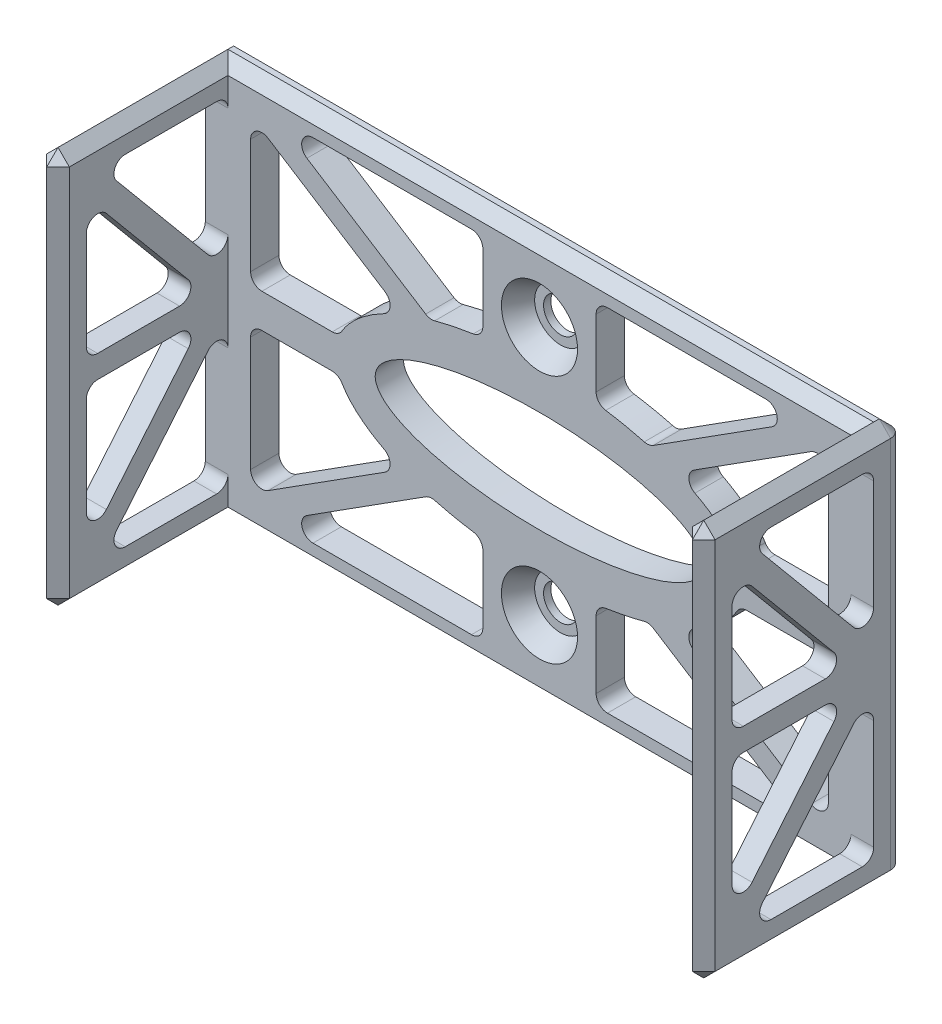
SolidWorks part; units mm, degrees
material "6061-T6 (SS)"
ref_plane "Front Plane" through (0, 0, 0) normal (0, 0, 1) x (1, 0, 0)
ref_plane "Top Plane" through (0, 0, 0) normal (0, 1, 0) x (1, 0, 0)
ref_plane "Right Plane" through (0, 0, 0) normal (1, 0, 0) x (0, 0, -1)
sketch "Sketch1" plane through (0, 0, 0) normal (0, 0, 1) x (1, 0, 0)
  line L1 (-55, 35) -> (55, 35)
  line L2 (-55, 35) -> (-55, -35)
  line L3 (-55, -35) -> (55, -35)
  line L4 (55, 35) -> (55, -35)
  line L5 (-55, 35) -> (55, -35) construction
  line L6 (-55, -35) -> (55, 35) construction
  circle A0 centre (0, 22) radius 3
  circle A1 centre (0, -22) radius 3
  point P0 (0, 0)
  dimension "D4" = 6
  dimension "D5" = 6
  dimension "D1" = 70
  dimension "D2" = 110
  dimension "D3" = 13
  dimension "D6" = 13
extrude "Boss-Extrude1" add sketch "Sketch1" along normal blind 5
sketch "Sketch2" plane through (0, 0, 5) normal (0, 0, 1) x (1, 0, 0)
  circle A0 centre (0, 22) radius 6.72
  circle A1 centre (0, -22) radius 6.72
  dimension "D1" = 13.44
  dimension "D2" = 13.44
extrude "Cut-Extrude1" cut sketch "Sketch2" against normal blind 3.72 draft 30
sketch "Sketch3" plane through (0, 0, 5) normal (0, 0, 1) x (1, 0, 0)
  line L0 (0, 0) -> (-55, 35) construction
  line L1 (0, 0) -> (-55, -35) construction
  line L2 (0, 0) -> (-13.5, 0) construction
  line L4 (-13.5, 0) -> (55, 0) construction
  line L5 (55, -35) -> (55, 35) construction
  line L6 (0, 0) -> (55, -35) construction
  line L7 (0, 0) -> (55, 35) construction
  line L8 (0, 0) -> (-55, 0) construction
  line L9 (-55, 35) -> (-55, -35) construction
  line L10 (-51, 28.8986) -> (-51, 3)
  line L11 (-51, 3) -> (-10.3022, 3)
  line L12 (-10.3022, 3) -> (-51, 28.8986)
  line L13 (-51, -3) -> (-51, -28.8986)
  line L14 (-51, -28.8986) -> (-10.3022, -3)
  line L15 (-10.3022, -3) -> (-51, -3)
  line L16 (-46.8517, 31) -> (-10, 7.5489)
  line L17 (-10, 7.5489) -> (-10, 31)
  line L18 (-10, 31) -> (-46.8517, 31)
  line L19 (-10, -7.5489) -> (-46.8517, -31)
  line L20 (-46.8517, -31) -> (-10, -31)
  line L21 (-10, -31) -> (-10, -7.5489)
  line L22 (0, 35) -> (0, -35) construction
  line L25 (-0.8631, 0.5493) -> (-0.8369, -0.5325) construction
  line L26 (55, 35) -> (-55, 35) construction
  line L27 (-55, -35) -> (55, -35) construction
  line L28 (46.8517, -31) -> (10, -31)
  line L29 (10, -7.5489) -> (46.8517, -31)
  line L30 (10, -31) -> (10, -7.5489)
  line L31 (51, -28.8986) -> (10.3022, -3)
  line L32 (51, -3) -> (51, -28.8986)
  line L33 (10.3022, -3) -> (51, -3)
  line L34 (51, 3) -> (10.3022, 3)
  line L35 (51, 28.8986) -> (51, 3)
  line L36 (10.3022, 3) -> (51, 28.8986)
  line L37 (10, 7.5489) -> (10, 31)
  line L38 (46.8517, 31) -> (10, 7.5489)
  line L39 (10, 31) -> (46.8517, 31)
  ellipse E0 centre (0, 0) end of major axis (36, 0) minor radius 16
  point P38 (-10, 19.2745)
  point P39 (-27.5, 0)
  point P40 (-30.6511, -15.9493)
  dimension "D2" = 4
  dimension "D3" = 10
  dimension "D4" = 4
  dimension "D5" = 1
  dimension "D6" = 3
  dimension "D7" = 3
  dimension "D8" = 3
  dimension "D9" = 3
  dimension "D10" = 1
  dimension "D11" = 4
  dimension "D12" = 10
  dimension "D13" = 19
  dimension "D14" = 19
extrude "Cut-Extrude2" cut sketch "Sketch3" against normal through all contours E0 L17 L18 L16 | E0 L12 L10 L11 | E0 L15 L13 L14 | E0 L19 L20 L21 | E0 L30 L28 L29 | E0 L31 L32 L33 | E0 L34 L35 L36 | E0 L38 L39 L37 region at (-41.5374, 13.3204, 5) region at (-23.1546, 24.2306, 5) region at (-41.5374, -13.3204, 5) region at (23.1546, 24.2306, 5) region at (-23.1546, -24.2306, 5) region at (41.5374, 13.3204, 5) region at (23.1546, -24.2306, 5) region at (41.5374, -13.3204, 5)
sketch "Sketch5" plane through (0, 0, 5) normal (0, 0, 1) x (1, 0, 0)
  ellipse E0 centre (0, 0) end of major axis (29, 0) minor radius 9
  dimension "D1" = 7
  dimension "D2" = 7
extrude "Cut-Extrude3" cut sketch "Sketch5" against normal through all
sketch "Sketch6" plane through (-55, 0, 0) normal (-1, 0, 0) x (0, 0, 1)
  line L0 (5, -35) -> (0, -35) construction
  line L1 (0, 35) -> (35, 35)
  line L2 (0, 35) -> (0, -35)
  line L3 (0, -35) -> (35, -35)
  line L4 (35, 35) -> (35, -35)
  dimension "D1" = 35
extrude "Boss-Extrude2" add sketch "Sketch6" along normal blind 4
mirror "Mirror1" about plane through (0, 0, 0) normal (1, 0, 0) of "Boss-Extrude2"
sketch "Sketch7" plane through (59, 0, 0) normal (1, 0, 0) x (0, 0, -1)
  line L0 (-35, 35) -> (0, 35) construction
  line L1 (-27.3966, 30) -> (-5, 30)
  line L2 (-30, 26.8759) -> (-30, 2)
  line L3 (-27.3966, -30) -> (-5, -30)
  line L4 (-5, 30) -> (-5, 3.1241)
  line L5 (0, -35) -> (-35, -35) construction
  line L6 (0, 35) -> (0, -35) construction
  line L7 (-35, -35) -> (-35, 35) construction
  line L8 (-30, 30) -> (-5, 0) construction
  line L9 (-5, 0) -> (-30, -30) construction
  line L10 (-27.3966, 30) -> (-5, 3.1241)
  line L11 (-30, 26.8759) -> (-9.2701, 2)
  line L12 (-9.2701, -2) -> (-30, -26.8759)
  line L13 (-27.3966, -30) -> (-5, -3.1241)
  line L14 (-9.2701, 2) -> (-30, 2)
  line L15 (-30, -2) -> (-9.2701, -2)
  line L16 (-30, 0) -> (-5, 0) construction
  line L17 (-30, -30) -> (-35, -35) construction
  line L18 (-35, 35) -> (-30, 30) construction
  line L19 (-30, -2) -> (-30, -26.8759)
  line L20 (-5, -3.1241) -> (-5, -30)
  dimension "D1" = 5
  dimension "D2" = 5
  dimension "D3" = 5
  dimension "D4" = 5
  dimension "D5" = 2
  dimension "D6" = 2
  dimension "D7" = 2
  dimension "D8" = 2
  dimension "D9" = 2
  dimension "D10" = 2
extrude "Cut-Extrude4" cut sketch "Sketch7" against normal through all both and the other way through all
fillet "Fillet2" radius 2 58 edges at (10, -15.3703, 2.5) (10, -31, 2.5) (19.3427, -13.4943, 2.5) (46.8517, -31, 2.5) (51, -28.8986, 2.5) (24.2015, -11.845, 2.5) (35.3615, -3, 2.5) (51, -3, 2.5) (35.3615, 3, 2.5) (24.2015, 11.845, 2.5) (51, 3, 2.5) (51, 28.8986, 2.5) (10, 31, 2.5) (46.8517, 31, 2.5) (19.3427, 13.4943, 2.5) (10, 15.3703, 2.5) (-10, -31, 2.5) (-10, -15.3703, 2.5) (-19.3427, -13.4943, 2.5) (-46.8517, -31, 2.5) (-51, -28.8986, 2.5) (-24.2015, -11.845, 2.5) (-35.3615, -3, 2.5) (-51, -3, 2.5) (-51, 3, 2.5) (-35.3615, 3, 2.5) (-24.2015, 11.845, 2.5) (-51, 28.8986, 2.5) (-19.3427, 13.4943, 2.5) (-10, 15.3703, 2.5) (-10, 31, 2.5) (-46.8517, 31, 2.5) (57, -30, 5) (57, 26.8759, 30) (57, 30, 27.3966) (57, 2, 30) (57, -2, 30) (57, -26.8759, 30) (57, -30, 27.3966) (57, 3.1241, 5) (57, 2, 9.2701) (57, -3.1241, 5) (57, -2, 9.2701) (57, 30, 5) (-57, -2, 30) (-57, 30, 27.3966) (-57, 26.8759, 30) (-57, 2, 9.2701) (-57, -2, 9.2701) (-57, -3.1241, 5) (-57, 2, 30) (-57, -30, 27.3966) (-57, -26.8759, 30) (-57, -30, 5) (-57, 3.1241, 5) (-57, 30, 5) (-59, 0, 0) (59, 0, 0)
sketch "Sketch4" plane through (0, 0, 0) normal (0, 0, -1) x (-1, 0, 0)
  line L0 (57, -35) -> (-57, -35) construction
  line L1 (-15, 35) -> (15, 35)
  line L2 (-15, 35) -> (-15, -35)
  line L3 (-15, -35) -> (15, -35)
  line L4 (15, 35) -> (15, -35)
  line L5 (-15, 35) -> (15, -35) construction
  line L6 (-15, -35) -> (15, 35) construction
  point P0 (0, 0)
  dimension "D1" = 30
split line "Split Line1"
chamfer "Chamfer2" distance 2 angle 45 28 edges at (0, 35, 5) (0, -35, 5) (-36, -35, 0) (0, -35, 0) (36, -35, 0) (36, 35, 0) (0, 35, 0) (-36, 35, 0) (-59, -35, 18.5) (-57, -35, 35) (-55, -35, 20) (55, -35, 20) (57, -35, 35) (59, -35, 18.5) (59, 35, 18.5) (57, 35, 35) (55, 35, 20) (-55, 35, 20) (-57, 35, 35) (-59, 35, 18.5) (59, 0, 35) (55, 0, 35) (-59, 0, 35) (-55, 0, 35) (-58.4142, -35, 0.5858) (58.4142, -35, 0.5858) (58.4142, 35, 0.5858) (-58.4142, 35, 0.5858)
